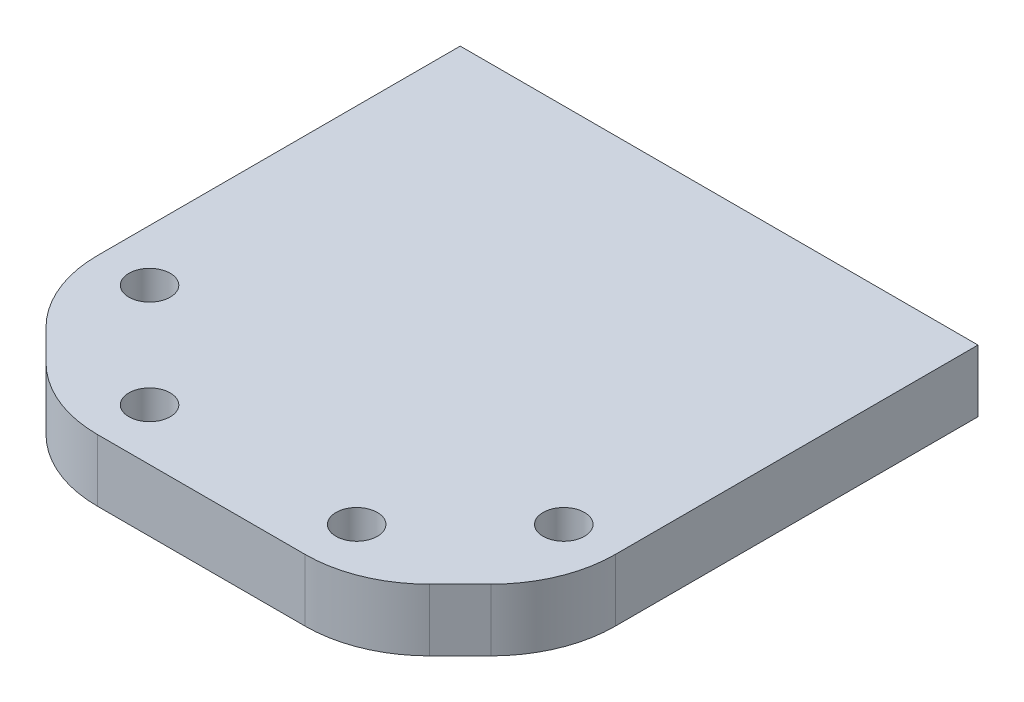
SolidWorks part; units mm, degrees
ref_plane "Alzado" through (0, 0, 0) normal (0, 0, 1) x (1, 0, 0)
ref_plane "Planta" through (0, 0, 0) normal (0, 1, 0) x (1, 0, 0)
ref_plane "Vista lateral" through (0, 0, 0) normal (1, 0, 0) x (0, 0, -1)
sketch "Croquis1" plane through (0, 0, 0) normal (0, 1, 0) x (1, 0, 0)
  line L0 (-5.0147, 0) -> (5.0147, 0)
  line L1 (-12.5, 25) -> (-12.5, 7.4853)
  line L2 (12.5, 25) -> (-12.5, 25)
  line L3 (-10.7426, 3.2426) -> (-9.2574, 1.7574)
  line L4 (0, 25) -> (0, 0) construction
  line L5 (-10, 7.5) -> (10, 7.5) construction
  line L6 (-5, 2.5) -> (5, 2.5) construction
  line L7 (12.5, 25) -> (12.5, 7.4853)
  line L8 (10.7426, 3.2426) -> (9.2574, 1.7574)
  circle A0 centre (-10, 7.5) radius 1
  circle A1 centre (-5, 2.5) radius 1
  circle A2 centre (10, 7.5) radius 1
  circle A3 centre (5, 2.5) radius 1
  arc A4 (12.5, 7.4853) -> (10.7426, 3.2426) centre (6.5, 7.4853) cw
  arc A5 (5.0147, 0) -> (9.2574, 1.7574) centre (5.0147, 6) ccw
  arc A6 (-12.5, 7.4853) -> (-10.7426, 3.2426) centre (-6.5, 7.4853) ccw
  arc A7 (-5.0147, 0) -> (-9.2574, 1.7574) centre (-5.0147, 6) cw
  point P2 (0, 0)
  point P6 (0, 25)
  point P18 (0, 7.5)
  point P19 (0, 2.5)
  point P23 (12.5, 5)
  point P26 (7.5, 0)
  point P29 (-12.5, 5)
  point P32 (-7.5, 0)
  dimension "D5" = 2
  dimension "D10" = 6
  dimension "D1" = 15
  dimension "D2" = 25
  dimension "D3" = 20
  dimension "D4" = 25
  dimension "D6" = 2.5
  dimension "D7" = 2.5
  dimension "D8" = 5
  dimension "D9" = 5
sheet metal parameters "Chapa metálica1" thickness 3 parameters "D1"=0.7366, "Espesor"=3
base flange "Brida base1" sketch "Croquis1" thickness 3 reverse thickness direction no parameters "D1"=0.7366
flat pattern "Chapa desplegada1" [suppressed]
sketch "Líneas de pliegue1" plane through (0, 0, 0) normal (0, 1, 0) x (-1, 0, 0)
sketch3d "Cuadro delimitador1" [suppressed]
  line L0 (12.5, -22.5, 0) -> (-12.5, -22.5, 0) construction
  line L1 (12.5, -7.5, 0) -> (-12.5, -7.5, 0) construction
  line L2 (12.5, -22.5, 0) -> (12.5, -7.5, 0) construction
  line L3 (-12.5, -22.5, 0) -> (-12.5, -7.5, 0) construction
